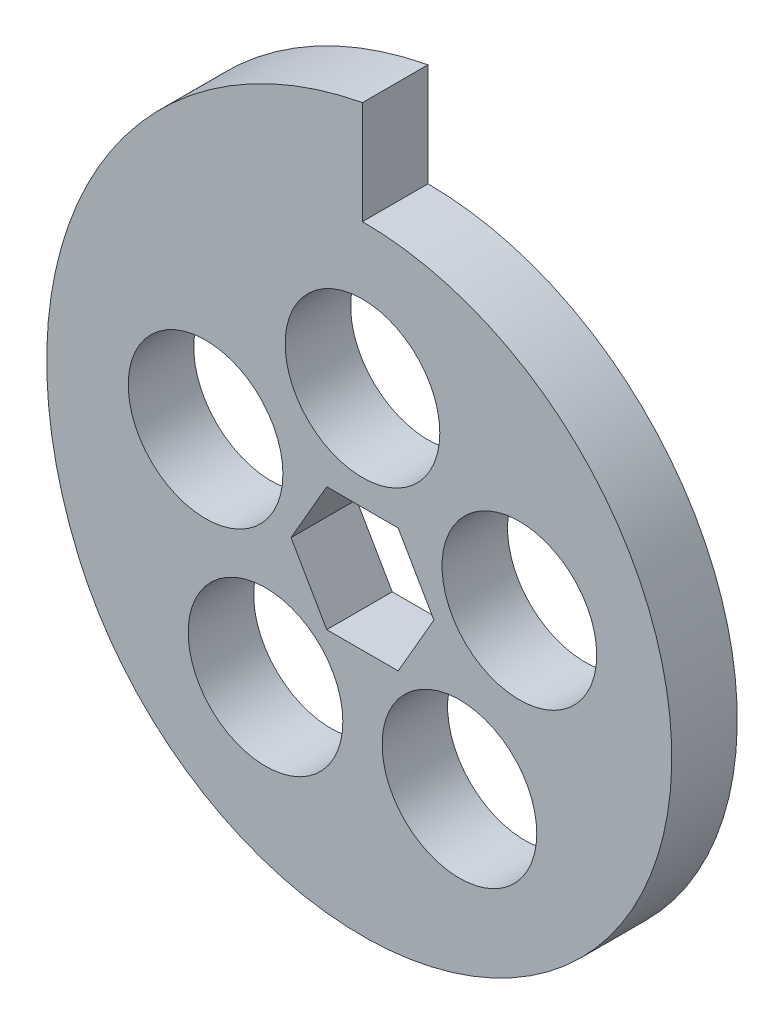
SolidWorks part; units mm, degrees
material "Commercially Pure titanium (Ti-55)  UNS R50550*"
ref_plane "Front Plane" through (0, 0, 0) normal (0, 0, 1) x (1, 0, 0)
ref_plane "Top Plane" through (0, 0, 0) normal (0, 1, 0) x (1, 0, 0)
ref_plane "Right Plane" through (0, 0, 0) normal (1, 0, 0) x (0, 0, -1)
sketch "Sketch3" plane through (0, 0, 0) normal (0, 0, 1) x (1, 0, 0)
  line L5 (0, 30) -> (0, 40)
  line L6 (6.9282, 0) -> (3.4641, 6)
  line L7 (3.4641, 6) -> (-3.4641, 6)
  line L8 (-3.4641, 6) -> (-6.9282, 0)
  line L9 (-6.9282, 0) -> (-3.4641, -6)
  line L10 (-3.4641, -6) -> (3.4641, -6)
  line L11 (3.4641, -6) -> (6.9282, 0)
  circle A2 centre (0, 0) radius 30 construction
  circle A3 centre (0, 0) radius 6 construction
  circle A4 centre (0, 16) radius 7.5
  circle A5 centre (15.2169, 4.9443) radius 7.5
  circle A6 centre (9.4046, -12.9443) radius 7.5
  circle A7 centre (-9.4046, -12.9443) radius 7.5
  circle A8 centre (-15.2169, 4.9443) radius 7.5
  arc A9 (0, 40) -> (-27.5501, -11.874) centre (7.013, 3.0226) ccw
  arc A10 (0, 30) -> (-27.5501, -11.874) centre (0, 0) cw
  point P3 (0, 0)
  point P25 (0, 0)
  dimension "D2" = 10
  dimension "D1" = 60
  dimension "D4" = 15
  dimension "D3" = 12
  dimension "D5" = 16
  dimension "D6" = 5
extrude "Boss-Extrude1" add sketch "Sketch3" along normal blind 6.35
